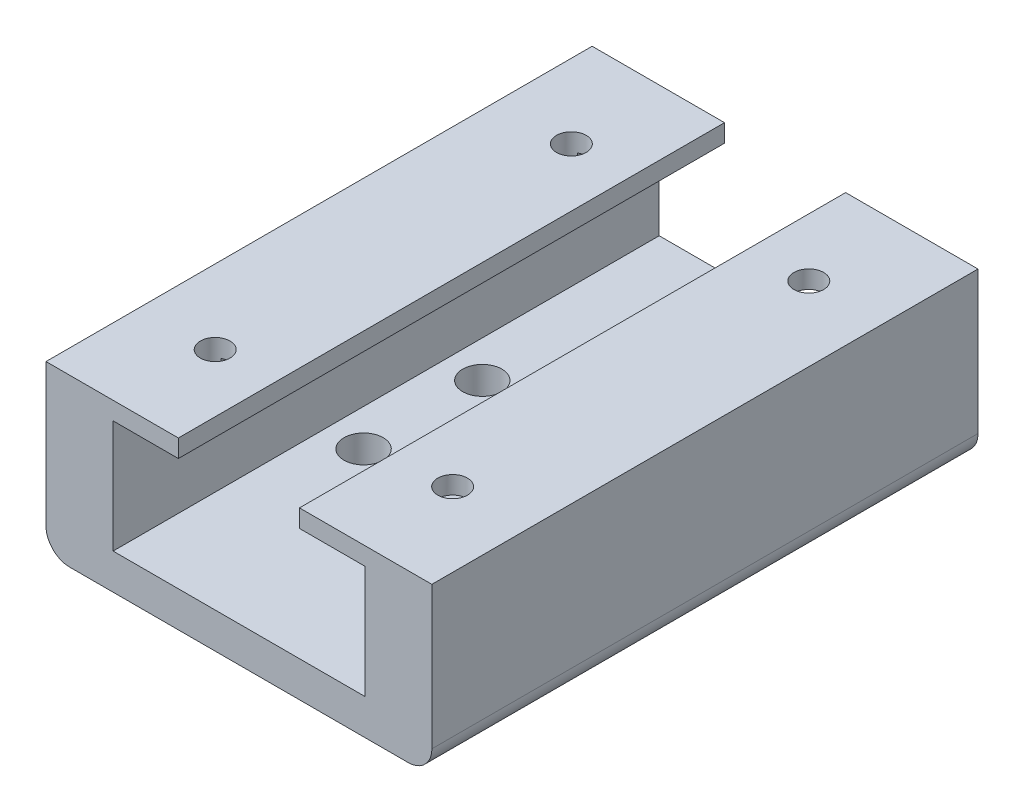
SolidWorks part; units mm, degrees
ref_plane "前视基准面" through (0, 0, 0) normal (0, 0, 1) x (1, 0, 0)
ref_plane "上视基准面" through (0, 0, 0) normal (0, 1, 0) x (1, 0, 0)
ref_plane "右视基准面" through (0, 0, 0) normal (1, 0, 0) x (0, 0, -1)
sketch "草图1" plane through (0, 0, 0) normal (0, 1, 0) x (1, 0, 0)
  line L1 (16.25, -23) -> (-16.25, -23)
  line L2 (16.25, -23) -> (16.25, 23)
  line L3 (16.25, 23) -> (-16.25, 23)
  line L4 (-16.25, -23) -> (-16.25, 23)
  line L5 (16.25, -23) -> (-16.25, 23) construction
  line L6 (16.25, 23) -> (-16.25, -23) construction
  point P0 (0, 0)
  dimension "D1" = 32.5
  dimension "D2" = 46
extrude "凸台-拉伸1" add sketch "草图1" along normal blind 14
sketch "草图2" plane through (0, 0, -23) normal (0, 0, -1) x (-1, 0, 0)
  line L0 (-16.25, 14) -> (16.25, 14) construction
  line L1 (-5.1, 12.5) -> (5.1, 12.5)
  line L2 (-5.1, 12.5) -> (-5.1, 14)
  line L3 (-5.1, 14) -> (5.1, 14)
  line L4 (5.1, 12.5) -> (5.1, 14)
  line L5 (-5.1, 12.5) -> (5.1, 14) construction
  line L6 (-5.1, 14) -> (5.1, 12.5) construction
  line L8 (-10.6, 3) -> (10.6, 3)
  line L9 (-10.6, 3) -> (-10.6, 12.5)
  line L10 (-10.6, 12.5) -> (10.6, 12.5)
  line L11 (10.6, 3) -> (10.6, 12.5)
  line L12 (-10.6, 3) -> (10.6, 12.5) construction
  line L13 (-10.6, 12.5) -> (10.6, 3) construction
  point P0 (0, 13.25)
  point P9 (0, 7.75)
  line M7 (16.25, 14) -> (-16.25, 14)
  dimension "D1" = 1.5
  dimension "D2" = 10.2
  dimension "D3" = 21.2
  dimension "D4" = 11
  dimension "D5" = 0
extrude "切除-拉伸2" cut sketch "草图2" against normal through all contours L1 L4 L2 M7 | L8 L11 L10 L1 L9 region at (0, 13.25, -23) region at (0, 7.75, -23)
sketch "草图4" plane through (0, 0, 0) normal (0, -1, 0) x (1, 0, 0)
  line L1 (-7.5, -5) -> (7.5, -5) construction
  line L2 (-7.5, -5) -> (-7.5, 5) construction
  line L3 (-7.5, 5) -> (7.5, 5) construction
  line L4 (7.5, -5) -> (7.5, 5) construction
  line L5 (-7.5, -5) -> (7.5, 5) construction
  line L6 (-7.5, 5) -> (7.5, -5) construction
  circle A0 centre (-7.5, 5) radius 1.65
  circle A1 centre (7.5, 5) radius 1.65
  circle A2 centre (7.5, -5) radius 1.65
  circle A3 centre (-7.5, -5) radius 1.65
  point P0 (0, 0)
  dimension "D3" = 3.3
  dimension "D4" = 3.3
  dimension "D5" = 3.3
  dimension "D6" = 3.3
  dimension "D1" = 15
  dimension "D2" = 10
extrude "切除-拉伸3" cut sketch "草图4" against normal up to next
sketch "草图5" plane through (0, 14, 0) normal (0, 1, 0) x (1, 0, 0)
  line L1 (-10, -15) -> (10, -15) construction
  line L2 (-10, -15) -> (-10, 15) construction
  line L3 (-10, 15) -> (10, 15) construction
  line L4 (10, -15) -> (10, 15) construction
  line L5 (-10, -15) -> (10, 15) construction
  line L6 (-10, 15) -> (10, -15) construction
  circle A0 centre (-10, 15) radius 1.25
  circle A1 centre (10, 15) radius 1.25
  circle A2 centre (10, -15) radius 1.25
  circle A3 centre (-10, -15) radius 1.25
  point P0 (0, 0)
  dimension "D3" = 2.5
  dimension "D4" = 2.5
  dimension "D5" = 2.5
  dimension "D6" = 2.5
  dimension "D1" = 30
  dimension "D2" = 20
extrude "切除-拉伸4" cut sketch "草图5" against normal blind 2
fillet "圆角1" radius 2 2 edges at (16.25, 0, 0) (-16.25, 0, 0)
equation "\"33.5.00mm\"=34"
